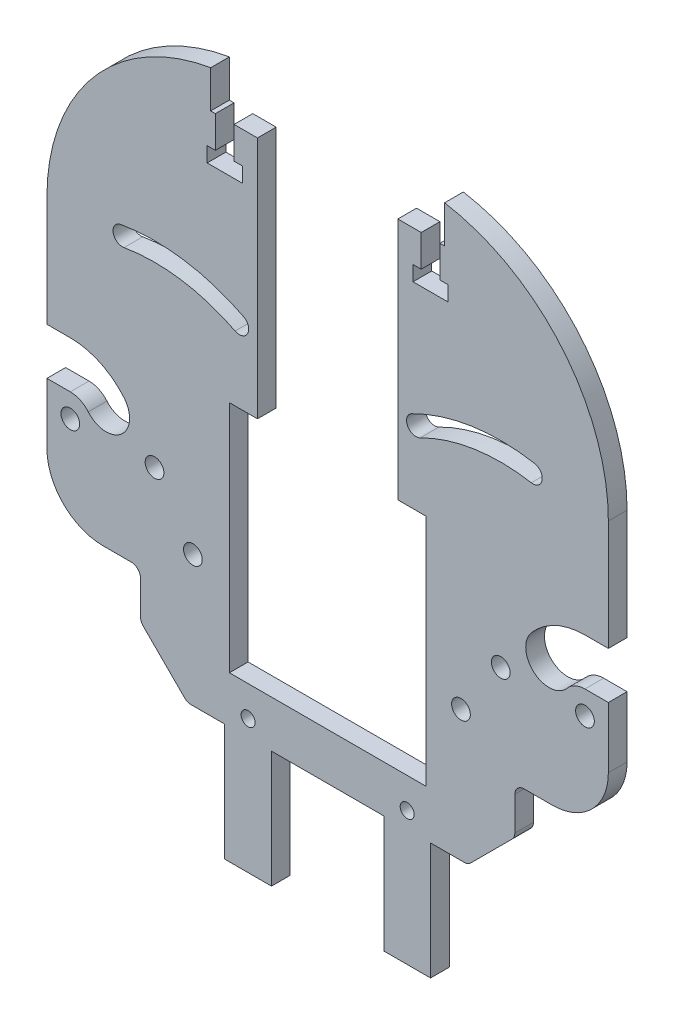
SolidWorks part; units mm, degrees
material "Acrylic (Medium-high impact)"
ref_plane "Front Plane" through (0, 0, 0) normal (0, 0, 1) x (1, 0, 0)
ref_plane "Top Plane" through (0, 0, 0) normal (0, 1, 0) x (1, 0, 0)
ref_plane "Right Plane" through (0, 0, 0) normal (1, 0, 0) x (0, 0, -1)
sketch "Sketch1" plane through (0, 0, 0) normal (0, 0, 1) x (1, 0, 0)
  line L0 (0, 0) -> (0, -98.0129) construction
  line L1 (-40, 60) -> (-25, 60)
  line L2 (-40, 60) -> (-40, -60)
  line L3 (-40, -60) -> (-22, -60)
  line L4 (40, 60) -> (40, -60)
  line L5 (-40, 60) -> (40, -60) construction
  line L6 (-40, -60) -> (40, 60) construction
  line L7 (21, 0) -> (21, -50)
  line L8 (0, 0) -> (0, 75) construction
  line L9 (-21, -50) -> (21, -50)
  line L10 (15, 0) -> (15, 52)
  line L11 (-15, 0) -> (-15, 52)
  line L12 (-15, 0) -> (-15, 85.1588) construction
  line L13 (0, 0) -> (0, 85.1588) construction
  line L14 (15, 0) -> (15, 85.1588) construction
  line L15 (25, 60) -> (40, 60)
  line L16 (-15, 0) -> (-21, 0)
  line L17 (15, 0) -> (21, 0)
  line L18 (-21, 0) -> (-21, -50)
  line L19 (-12, -60) -> (12, -60)
  line L21 (-15, 52) -> (-25, 52)
  line L22 (-25, 60) -> (-25, 52)
  line L23 (22, -60) -> (22, -85)
  line L24 (22, -85) -> (12, -85)
  line L25 (15, 52) -> (25, 52)
  line L26 (25, 60) -> (25, 52)
  line L27 (12, -60) -> (12, -85)
  line L28 (22, -60) -> (40, -60)
  line L29 (-12, -60) -> (-12, -85)
  line L30 (-12, -85) -> (-22, -85)
  line L31 (-22, -60) -> (-22, -85)
  point P0 (0, 0)
  dimension "D1" = 120
  dimension "D2" = 80
  dimension "D3" = 50
  dimension "D4" = 8
  dimension "D5" = 110
  dimension "D8" = 8
  dimension "D9" = 50
  dimension "D10" = 25
  dimension "D11" = 42
  dimension "D12" = 25
  dimension "D13" = 10
  dimension "D14" = 24
  dimension "D15" = 12
  dimension "D6" = 15
  dimension "D7" = 15
extrude "Boss-Extrude1" add sketch "Sketch1" along normal blind 4
sketch "Sketch2" plane through (0, 0, 0) normal (0, 0, -1) x (-1, 0, 0)
  line L1 (-21, 0) -> (-21, -50) construction
  line L2 (40, -60) -> (22, -60) construction
  line L3 (28.8, -32) -> (28.8, 8.3751) construction
  line L4 (22, -85) -> (12, -85) construction
  line L5 (-12, -85) -> (-22, -85) construction
  line L6 (21, -50) -> (21, 0) construction
  line L7 (-28.5, -12) -> (-28.5, -69.2337) construction
  line L9 (40, -60) -> (22, -60) construction
  circle A0 centre (-28.5, -32) radius 2
  circle A1 centre (17, -56.5) radius 1.5
  circle A2 centre (28.8, -32) radius 2
  circle A3 centre (-17, -56.5) radius 1.5
  point P21 (17, -85)
  point P24 (-17, -85)
  dimension "D1" = 4
  dimension "D6" = 3
  dimension "D2" = 7.5
  dimension "D3" = 57.3
  dimension "D4" = 28
  dimension "D5" = 28
  dimension "D7" = 3.5
extrude "Cut-Extrude1" cut sketch "Sketch2" against normal through all
ref_plane "Plane1" through (0, 0, -2) normal (0, 0, 1) x (1, 0, 0)
sketch "Sketch4" plane through (0, 0, 4) normal (0, 0, 1) x (1, 0, 0)
  line L1 (-40, 60) -> (-60, 60)
  line L2 (-40, 60) -> (-40, -40)
  line L3 (-40, -40) -> (-60, -40)
  line L4 (-60, 60) -> (-60, -40)
  line L5 (40, 60) -> (60, 60)
  line L6 (40, 60) -> (40, -40)
  line L7 (40, -40) -> (60, -40)
  line L8 (60, 60) -> (60, -40)
  dimension "D1" = 20
  dimension "D2" = 20
  dimension "D3" = 100
  dimension "D4" = 100
extrude "Boss-Extrude2" add sketch "Sketch4" against normal blind 4
fillet "Fillet3" radius 42 2 edges at (60, 60, 2) (-60, 60, 2)
fillet "Fillet4" radius 12 2 edges at (60, -40, 2) (-60, -40, 2)
sketch "Sketch7" plane through (0, 0, 0) normal (0, 0, 1) x (1, 0, 0)
  line L1 (-60, 18.5874) -> (-60, -28) construction
  line L2 (60, -28) -> (60, 18.5874) construction
  line L3 (22, -60) -> (40, -60) construction
  line L4 (-40, -60) -> (-22, -60) construction
  circle A0 centre (-55, -20) radius 2
  circle A1 centre (55, -20) radius 2
  circle A2 centre (-37, -20) radius 2
  circle A3 centre (37, -20) radius 2
  point P10 (-60, -4.7063)
  dimension "D3" = 5
  dimension "D4" = 5
  dimension "D5" = 4
  dimension "D6" = 4
  dimension "D7" = 4
  dimension "D1" = 40
  dimension "D2" = 40
  dimension "D8" = 18
  dimension "D9" = 18
extrude "Cut-Extrude3" cut sketch "Sketch7" along normal through all
chamfer "Chamfer1" distance 10 angle 45 2 edges at (-40, -60, 2) (40, -60, 2)
fillet "Fillet8" radius 2 6 edges at (-30, -60, 2) (-40, -50, 2) (30, -60, 2) (40, -50, 2)
sketch "Sketch8" plane through (0, 0, 0) normal (0, 0, -1) x (-1, 0, 0)
  line L0 (0, 0) -> (0, 75) construction
  line L1 (0, 0) -> (0, 75)
  circle A0 centre (-37, -20) radius 40 construction
  arc A1 (-18.8713, 15.656) -> (-43.8713, 19.4054) centre (-37, -20) ccw construction
  arc A2 (-17.9648, 17.4388) -> (-44.2148, 21.3757) centre (-37, -20) ccw
  arc A3 (-19.7777, 13.8732) -> (-43.5277, 17.4351) centre (-37, -20) ccw
  arc A4 (-19.7777, 13.8732) -> (-17.9648, 17.4388) centre (-18.8713, 15.656) ccw
  arc A5 (-44.2148, 21.3757) -> (-43.5277, 17.4351) centre (-43.8713, 19.4054) ccw
  arc A6 (18.8713, 15.656) -> (43.8713, 19.4054) centre (37, -20) cw construction
  arc A7 (17.9648, 17.4388) -> (44.2148, 21.3757) centre (37, -20) cw
  arc A8 (19.7777, 13.8732) -> (43.5277, 17.4351) centre (37, -20) cw
  arc A9 (19.7777, 13.8732) -> (17.9648, 17.4388) centre (18.8713, 15.656) cw
  arc A10 (44.2148, 21.3757) -> (43.5277, 17.4351) centre (43.8713, 19.4054) cw
  point P5 (-31.0673, 19.5576)
  point P15 (31.0673, 19.5576)
  dimension "D1" = 80
  dimension "D2" = 2
  dimension "D3" = 25
extrude "Cut-Extrude4" cut sketch "Sketch8" against normal through all contours A7 A10 A8 A9 | A2 A5 A3 A4
sketch "Sketch9" plane through (0, 0, 4) normal (0, 0, 1) x (1, 0, 0)
  line L0 (-15, 52) -> (-25, 52) construction
  line L1 (-24, 52) -> (-20, 52)
  line L2 (-24, 52) -> (-24, 45.2)
  line L3 (-22, 40.3094) -> (-22, 51.6327) construction
  line L4 (-20, 52) -> (-20, 45.2)
  line L5 (-25, 52) -> (-25, 60) construction
  line L6 (-20, 45.2) -> (-18.25, 45.2)
  line L7 (-25.75, 45.2) -> (-24, 45.2)
  line L8 (-25.75, 45.2) -> (-25.75, 42)
  line L9 (-25.75, 42) -> (-18.25, 42)
  line L10 (-18.25, 45.2) -> (-18.25, 42)
  dimension "D1" = 3
  dimension "D2" = 2
  dimension "D3" = 2
  dimension "D4" = 7.5
  dimension "D5" = 3.2
  dimension "D6" = 10
  dimension "D7" = 3.75
extrude "Cut-Extrude5" cut sketch "Sketch9" against normal through all
mirror "Mirror1" about plane through (0, 0, 0) normal (1, 0, 0) of "Cut-Extrude5"
sketch "Sketch10" plane through (0, 0, 4) normal (0, 0, 1) x (1, 0, 0)
  line L0 (55, -5) -> (60, -5)
  line L1 (55, -20) -> (50.7738, -10.9369) construction
  line L2 (55, -15) -> (60, -15)
  line L3 (60, -28) -> (60, 18.5874) construction
  line L4 (60, -15) -> (60, -5)
  line L5 (55, -20) -> (55, -10) construction
  circle A0 centre (55, -20) radius 2 construction
  circle A1 centre (55, -20) radius 2
  arc A2 (55, -10) -> (47.3396, -13.5721) centre (55, -20) ccw construction
  arc A3 (55, -5) -> (43.5093, -10.3582) centre (55, -20) ccw
  arc A4 (55, -15) -> (51.1698, -16.7861) centre (55, -20) ccw
  arc A6 (43.5093, -10.3582) -> (51.1698, -16.7861) centre (47.3396, -13.5721) ccw
  point P5 (50.7738, -10.9369)
  dimension "D1" = 10
  dimension "D2" = 5
  dimension "D3" = 25
  dimension "D5" = 5
  dimension "D6" = 5
  dimension "D4" = 5
extrude "Cut-Extrude6" cut sketch "Sketch10" against normal through all
mirror "Mirror2" about plane through (0, 0, 0) normal (1, 0, 0) of "Cut-Extrude6"
